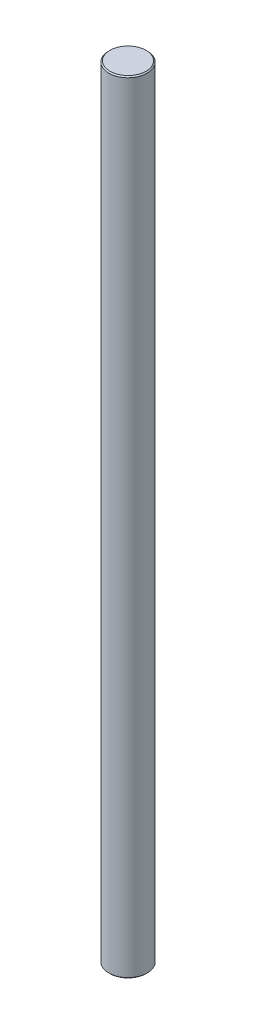
SolidWorks part; units mm, degrees
ref_plane "Front Plane" through (0, 0, 0) normal (0, 0, 1) x (1, 0, 0)
ref_plane "Top Plane" through (0, 0, 0) normal (0, 1, 0) x (1, 0, 0)
ref_plane "Right Plane" through (0, 0, 0) normal (1, 0, 0) x (0, 0, -1)
sketch "Sketch1" plane through (0, 0, 0) normal (0, 0, 1) x (1, 0, 0)
  line L1 (5, 101.5) -> (0, 101.5)
  line L2 (5, 101.5) -> (5, -101.5)
  line L3 (5, -101.5) -> (0, -101.5)
  line L4 (0, 101.5) -> (0, -101.5)
  line L5 (5, 101.5) -> (0, -101.5) construction
  line L6 (5, -101.5) -> (0, 101.5) construction
  point P0 (2.5, 0)
  dimension "D1" = 5
  dimension "D2" = 203
revolve "Revolve1" add sketch "Sketch1" angle 360 about L4 region at (2.5, 0, 0)
ref_axis "Axis1" through (0, -101.5, 0) along (0, 1, 0)
chamfer "Chamfer1" distance 0.3 angle 45 2 edges at (0, -101.5, 5) (0, 101.5, 5)
ref_plane "Plane1" through (0, 28, 0) normal (0, 1, 0) x (1, 0, 0)
ref_plane "Plane2" through (0, -28, 0) normal (0, -1, 0) x (-1, 0, 0)
